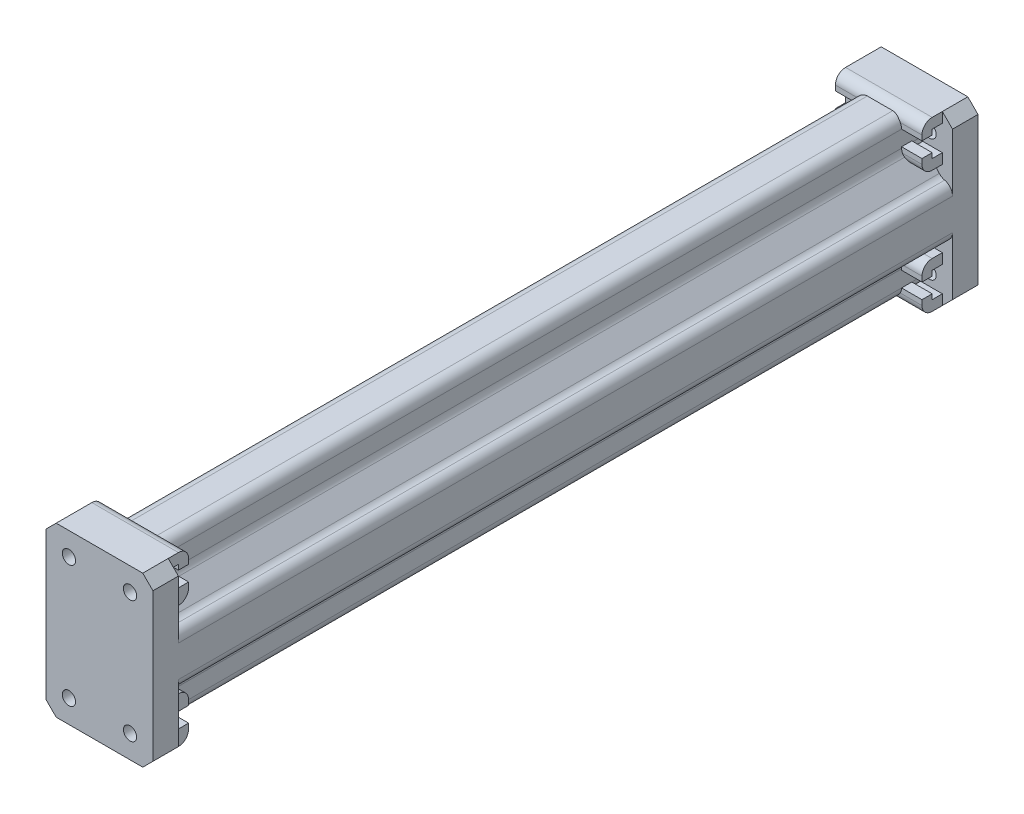
SolidWorks part; units mm, degrees
ref_plane "Front Plane" through (0, 0, 0) normal (0, 0, 1) x (1, 0, 0)
ref_plane "Top Plane" through (0, 0, 0) normal (0, 1, 0) x (1, 0, 0)
ref_plane "Right Plane" through (0, 0, 0) normal (1, 0, 0) x (0, 0, -1)
sketch "Sketch1" plane through (0, 0, 0) normal (0, 0, 1) x (1, 0, 0)
  line L0 (6, -12) -> (-6, 12) construction
  line L1 (-6, -12) -> (6, 12) construction
  line L2 (10.5, -16.5) -> (-10.5, -16.5)
  line L3 (10.5, -16.5) -> (10.5, 16.5)
  line L4 (10.5, 16.5) -> (-10.5, 16.5)
  line L5 (-10.5, -16.5) -> (-10.5, 16.5)
  line L6 (10.5, -16.5) -> (-10.5, 16.5) construction
  line L7 (10.5, 16.5) -> (-10.5, -16.5) construction
  line L8 (-8.5, 16.5) -> (-10.5, 14.5)
  line L9 (-6, 12) -> (6, 12) construction
  line L10 (-6, 12) -> (-6, -12) construction
  line L11 (-6, -12) -> (6, -12) construction
  line L12 (6, 12) -> (6, -12) construction
  line L13 (55, 0) -> (-55, 0) construction
  line L14 (-8.5, -16.5) -> (-10.5, -14.5)
  line L15 (0, -55) -> (0, 55) construction
  line L16 (8.5, -16.5) -> (10.5, -14.5)
  line L17 (8.5, 16.5) -> (10.5, 14.5)
  circle A16 centre (0, 0) radius 9
  circle A17 centre (-6, 12) radius 1.3
  circle A18 centre (6, 12) radius 1.3
  circle A19 centre (-6, -12) radius 1.3
  circle A20 centre (6, -12) radius 1.3
  point P1 (0, 0)
  point P4 (0, 0)
  dimension "D3" = 18
  dimension "D4" = 2.6
  dimension "D5" = 12
  dimension "D1" = 33
  dimension "D2" = 21
  dimension "D6" = 24
  dimension "D7" = 2
  dimension "D8" = 2
extrude "Boss-Extrude1" add sketch "Sketch1" along normal blind 5 contours A16 | L5 L2 L3 L4 A16 region at (0, -16.1088, 0) region at (0, 0, 0)
sketch "Sketch2" plane through (0, 0, 5) normal (0, 0, 1) x (1, 0, 0)
  line L1 (-2.5, 15.5) -> (2.5, 15.5)
  line L2 (-4.5, 13.5) -> (-4.5, 10.2604)
  line L3 (-2.5, -15.5) -> (2.5, -15.5)
  line L4 (4.5, 13.5) -> (4.5, 10.2604)
  line L5 (-4.5, 15.5) -> (4.5, -15.5) construction
  line L6 (-4.5, -15.5) -> (4.5, 15.5) construction
  line L7 (-10.5, 5) -> (-9.3981, 5)
  line L8 (-10.5, 5) -> (-10.5, -5)
  line L9 (-10.5, -5) -> (-9.3981, -5)
  line L10 (10.5, 5) -> (10.5, -5)
  line L11 (-10.5, 5) -> (10.5, -5) construction
  line L12 (-10.5, -5) -> (10.5, 5) construction
  line L16 (10.5, -14.5) -> (10.5, 14.5) construction
  line L17 (8.5, 16.5) -> (-8.5, 16.5) construction
  line L18 (-5.0052, 8.9317) -> (-7.9033, 5.6713)
  line L19 (2.75, 0) -> (-2.75, 0) construction
  line L20 (9.3981, 5) -> (10.5, 5)
  line L21 (-5.0052, -8.9317) -> (-7.9033, -5.6713)
  line L22 (0, -2.75) -> (0, 2.75) construction
  line L23 (5.0052, -8.9317) -> (7.9033, -5.6713)
  line L24 (5.0052, 8.9317) -> (7.9033, 5.6713)
  line L25 (9.3981, -5) -> (10.5, -5)
  line L26 (-4.5, -10.2604) -> (-4.5, -13.5)
  line L27 (4.5, -10.2604) -> (4.5, -13.5)
  arc A0 (-7.9033, 5.6713) -> (-9.3981, 5) centre (-9.3981, 7) cw
  arc A1 (-4.5, 10.2604) -> (-5.0052, 8.9317) centre (-6.5, 10.2604) cw
  arc A2 (-2.5, 15.5) -> (-4.5, 13.5) centre (-2.5, 13.5) ccw
  arc A3 (2.5, -15.5) -> (4.5, -13.5) centre (2.5, -13.5) ccw
  arc A4 (-2.5, -15.5) -> (-4.5, -13.5) centre (-2.5, -13.5) cw
  arc A5 (-7.9033, -5.6713) -> (-9.3981, -5) centre (-9.3981, -7) ccw
  arc A6 (-5.0052, -8.9317) -> (-4.5, -10.2604) centre (-6.5, -10.2604) cw
  arc A7 (4.5, -10.2604) -> (5.0052, -8.9317) centre (6.5, -10.2604) cw
  arc A8 (7.9033, -5.6713) -> (9.3981, -5) centre (9.3981, -7) cw
  arc A9 (7.9033, 5.6713) -> (9.3981, 5) centre (9.3981, 7) ccw
  arc A10 (5.0052, 8.9317) -> (4.5, 10.2604) centre (6.5, 10.2604) cw
  arc A11 (4.5, 13.5) -> (2.5, 15.5) centre (2.5, 13.5) ccw
  point P0 (0, 0)
  point P5 (0, 0)
  point P29 (-8.5, 5)
  point P32 (-4.5, 9.5)
  point P44 (-8.5, -5)
  point P47 (-4.5, -9.5)
  point P50 (4.5, -9.5)
  point P53 (8.5, -5)
  point P56 (8.5, 5)
  point P59 (4.5, 9.5)
  dimension "D1" = 9
  dimension "D6" = 2
  dimension "D7" = 2
  dimension "D8" = 2
  dimension "D9" = 2
  dimension "D2" = 10
  dimension "D3" = 1
  dimension "D4" = 6
  dimension "D5" = 2
extrude "Boss-Extrude2" add sketch "Sketch2" along normal blind 76
fillet "Fillet1" radius 2 4 edges at (10.5, -5, 43) (10.5, 5, 43) (-10.5, -5, 43) (-10.5, 5, 43)
ref_axis "Axis1" through (-6, 12, 5) along (0, 0, -1)
sketch "Sketch7" plane through (-4.5, 0, 0) normal (-1, 0, 0) x (0, 0, 1)
  line L0 (5, 14.5) -> (7, 14.5)
  line L1 (5, 14.5) -> (5, 9.5) construction
  line L2 (5, 9.5) -> (7, 9.5)
  line L3 (7, 14.5) -> (7, 13.5)
  line L4 (5, 16.5) -> (7, 16.5)
  line L5 (9, 14.5) -> (9, 13.5)
  line L6 (5, 7.5) -> (7, 7.5)
  line L7 (7, 13.5) -> (9, 13.5)
  line L8 (7, 10.5) -> (9, 10.5)
  line L9 (7, 10.5) -> (7, 9.5)
  line L10 (9, 10.5) -> (9, 9.5)
  line L11 (5, 16.5) -> (5, 14.5)
  line L12 (5, 9.5) -> (5, 7.5)
  line L13 (5, 16.5) -> (0, 16.5) construction
  line L15 (5, 3.1021) -> (5, 14.5) construction
  arc A0 (9, 9.5) -> (7, 7.5) centre (7, 9.5) cw
  arc A1 (9, 14.5) -> (7, 16.5) centre (7, 14.5) ccw
  dimension "D4" = 2
  dimension "D1" = 5
  dimension "D2" = 2
  dimension "D3" = 3
  dimension "D5" = 1
  dimension "D6" = 1
extrude "Boss-Extrude9" add sketch "Sketch7" along normal blind 9 from offset 5 offset against normal yes
mirror "Mirror8" about plane through (0, 0, 0) normal (1, 0, 0) of "Boss-Extrude9" second plane through (0, 0, 0) second plane normal (0, 1, 0)
sketch "Sketch5" [suppressed] plane through (0, 0, 5) normal (0, 0, 1) x (1, 0, 0)
  line L0 (-7.4793, 14.4844) -> (-9.1188, 11.9844) construction
  line L1 (-7.4793, 14.4844) -> (-4.4896, 14.4844) construction
  line L3 (-7.4793, 9.4844) -> (-4.4896, 9.4844) construction
  line L5 (-7.5873, 14.6844) -> (-9.3579, 11.9844)
  line L6 (-9.3579, 11.9844) -> (-7.5873, 9.2844)
  line L7 (-9.1188, 11.9844) -> (-7.4793, 9.4844) construction
  line L8 (-4.4896, 14.4844) -> (-2.8501, 11.9844) construction
  line L9 (-2.8501, 11.9844) -> (-4.4896, 9.4844) construction
  line L10 (-7.5873, 9.2844) -> (-4.3816, 9.2844)
  line L11 (-2.611, 11.9844) -> (-4.3816, 9.2844)
  line L12 (-4.3816, 14.6844) -> (-2.611, 11.9844)
  line L13 (-7.5873, 14.6844) -> (-4.3816, 14.6844)
  point P0 (-6, 12)
  dimension "D1" = 5
  dimension "D2" = 0.2
extrude "Cut-Extrude1" [suppressed] cut sketch "Sketch5" against normal blind 2.5 and the other way blind 0.5
mirror "Mirror5" [suppressed] about plane through (0, 0, 0) normal (0, 1, 0) second plane through (0, 0, 0) second plane normal (1, 0, 0)
fillet "Fillet2" [suppressed] radius 2
mirror "Mirror6" about plane through (9.3981, 7, 81) normal (0, 0, 1) of bodies 133 128
